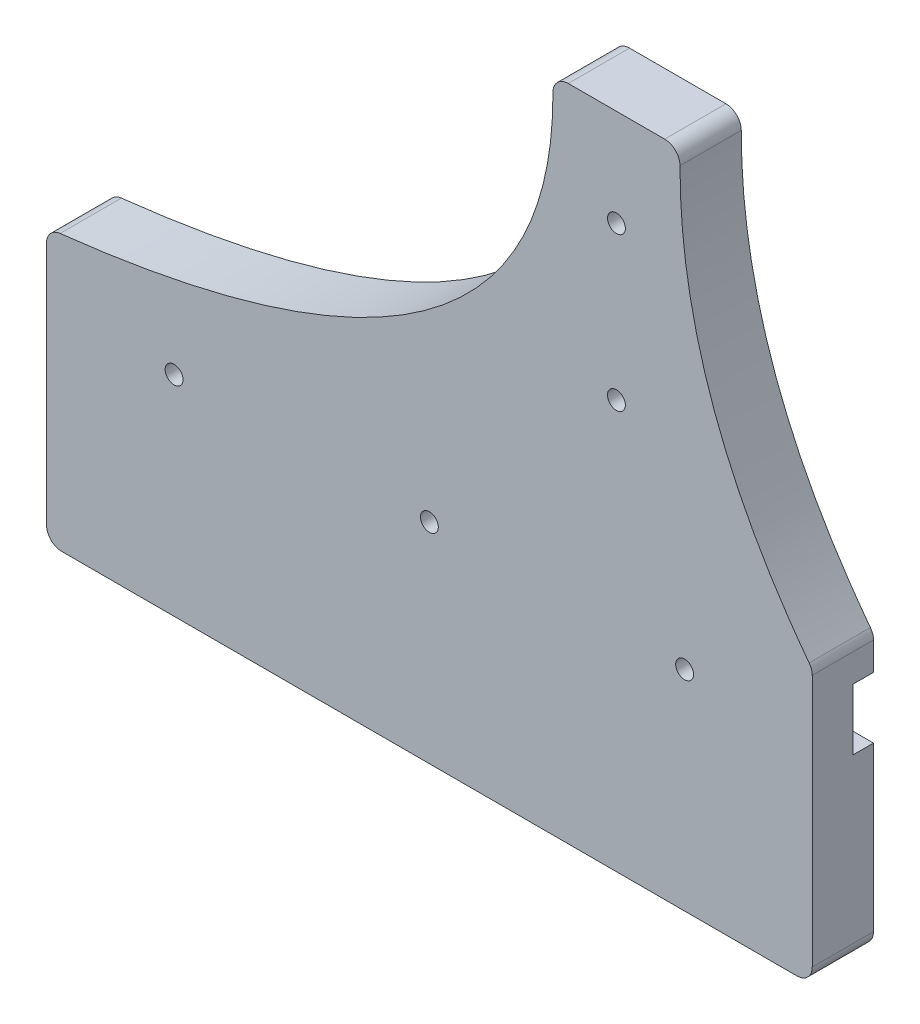
SolidWorks part; units mm, degrees
ref_plane "Ebene vorne" through (0, 0, 0) normal (0, 0, 1) x (1, 0, 0)
ref_plane "Ebene oben" through (0, 0, 0) normal (0, 1, 0) x (1, 0, 0)
ref_plane "Ebene rechts" through (0, 0, 0) normal (1, 0, 0) x (0, 0, -1)
sketch "Skizze1" plane through (0, 0, 0) normal (0, 0, 1) x (1, 0, 0)
  line L0 (24.14, 88) -> (49.14, 88)
  line L3 (75, 12.5) -> (75, -41)
  line L4 (75, -41) -> (-75, -41)
  line L9 (-75, -41) -> (-75, 12.5)
  line L13 (30.64, 81.5) -> (42.64, 81.5)
  line L14 (30.64, 81.5) -> (30.64, 26.5)
  line L15 (30.64, 26.5) -> (42.64, 26.5)
  line L16 (42.64, 81.5) -> (42.64, 26.5)
  line L17 (30.64, 81.5) -> (42.64, 26.5) construction
  line L18 (30.64, 26.5) -> (42.64, 81.5) construction
  line L19 (-75, 6) -> (75, 6)
  line L20 (-75, 6) -> (-75, -6)
  line L21 (-75, -6) -> (75, -6)
  line L22 (75, 6) -> (75, -6)
  line L23 (-75, 6) -> (75, -6) construction
  line L24 (-75, -6) -> (75, 6) construction
  line L26 (-75, 12.5) -> (75, 12.5) construction
  line L27 (24.14, 81.5) -> (49.14, 81.5) construction
  line L28 (-50, 0) -> (50, 0) construction
  line L29 (36.64, 69) -> (36.64, 39) construction
  circle A0 centre (-50, 0) radius 1.75
  circle A1 centre (0, 0) radius 1.75
  circle A2 centre (50, 0) radius 1.75
  circle A3 centre (36.64, 69) radius 1.75
  circle A4 centre (36.64, 39) radius 1.75
  spline S0 degree 2 poles (24.14, 88) (26.8075, 22.9626) (-75, 12.5) knots 0 0 0 1 1 1
  spline S1 degree 2 poles (49.14, 88) (47.9994, 47.6999) (75, 12.5) knots 0 0 0 1 1 1
  point P2 (0, -41)
  point P13 (36.64, 88)
  point P16 (36.64, 54)
  point P23 (0, 0)
  point P33 (0, 0)
  point P34 (0, 0)
  point P35 (36.64, 54)
  dimension "D12" = 3.5
  dimension "D13" = 3.5
  dimension "D14" = 3.5
  dimension "D16" = 3.5
  dimension "D17" = 3.5
  dimension "D2" = 25
  dimension "D3" = 150
  dimension "D4" = 35
  dimension "D5" = 36.64
  dimension "D6" = 6.5
  dimension "D7" = 69
  dimension "D8" = 6.5
  dimension "D9" = 12
  dimension "D10" = 55
  dimension "D11" = 12
  dimension "D15" = 100
  dimension "D18" = 30
extrude "Aufsatz-Linear austragen1" add sketch "Skizze1" along normal blind 12 contours S1 L0 S0 L9 L19 L3 L13 L16 L15 L14 | L16 L13 L14 L15 | L9 L21 L3 L19 | L21 L9 L4 L3 region at (18.2385, 29.5651, 0) region at (0, 4.4952, 0) region at (0, -23.5, 0) region at (36.64, 54, 0)
extrude "Schnitt-Linear austragen2" cut sketch "Skizze1<4>" along normal blind 4 contours L16 L13 L14 L15 | L20 L19 L22 L21 region at (36.64, 54, 0)
sketch "Skizze1<4>" plane through (0, 0, 0) normal (0, 0, 1) x (1, 0, 0) same geometry as "Skizze1"
fillet "Verrundung1" radius 3 6 edges at (75, -41, 6) (75, 12.5, 6) (49.14, 88, 6) (-75, -41, 6) (-75, 12.5, 6) (24.14, 88, 6)
